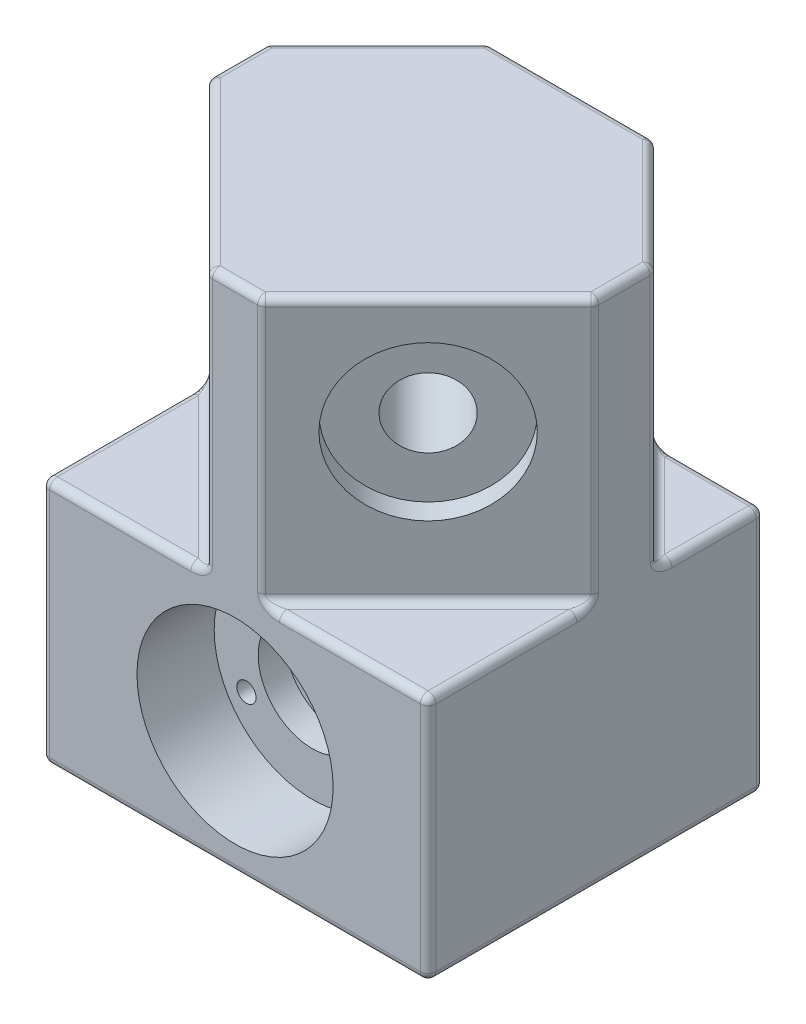
SolidWorks part; units mm, degrees
material "Stainless Steel (ferritic)"
ref_plane "Front Plane" through (0, 0, 0) normal (0, 0, 1) x (1, 0, 0)
ref_plane "Top Plane" through (0, 0, 0) normal (0, 1, 0) x (1, 0, 0)
ref_plane "Right Plane" through (0, 0, 0) normal (1, 0, 0) x (0, 0, -1)
sketch "Sketch1" plane through (0, 0, 0) normal (0, 1, 0) x (1, 0, 0)
  line L0 (-31.75, 31.75) -> (31.75, -31.75) construction
  line L1 (-31.75, 31.75) -> (31.75, 31.75)
  line L2 (-31.75, 31.75) -> (-31.75, -31.75)
  line L3 (-31.75, -31.75) -> (31.75, -31.75)
  line L4 (31.75, 31.75) -> (31.75, -31.75)
  dimension "D1" = 63.5
extrude "Boss-Extrude1" add sketch "Sketch1" along normal blind 66.2
sketch "Sketch2" plane through (0, 0, 31.75) normal (0, 0, 1) x (1, 0, 0)
  line L0 (-31.75, 0) -> (31.75, 0) construction
  circle A0 centre (0, 16) radius 12.7
  dimension "D1" = 25.4
  dimension "D2" = 16
extrude "Cut-Extrude4" cut sketch "Sketch2" against normal blind 10
sketch "Sketch3" plane through (0, 0, 21.75) normal (0, 0, 1) x (1, 0, 0)
  circle A0 centre (0, 16) radius 7
  dimension "D1" = 14
extrude "Cut-Extrude5" cut sketch "Sketch3" against normal blind 3.5
sketch "Sketch4" plane through (0, 0, 18.25) normal (0, 0, 1) x (1, 0, 0)
  circle A0 centre (0, 16) radius 6
  circle A1 centre (0, 16) radius 7 construction
  dimension "D1" = 1
extrude "Cut-Extrude6" cut sketch "Sketch4" against normal through all
sketch "Sketch5" plane through (0, 66.2, 0) normal (0, 1, 0) x (1, 0, 0)
  line L0 (0, -34.6734) -> (0, 38.8135) construction
  line L1 (13.935, -21.1434) -> (3.3284, -10.5368) construction
  line L2 (-31.75, -31.75) -> (31.75, -31.75) construction
  line L3 (3.3284, -31.75) -> (31.75, -3.3284)
  line L4 (31.75, -31.75) -> (31.75, 31.75) construction
  line L5 (31.75, -3.3284) -> (31.75, -31.75)
  line L6 (31.75, -31.75) -> (3.3284, -31.75)
  line L7 (3.3284, -10.5368) -> (0.5, -13.3652) construction
  line L8 (0.5, -13.3652) -> (11.1066, -23.9718) construction
  line L9 (-31.75, -31.75) -> (-3.3284, -31.75)
  line L10 (-31.75, -3.3284) -> (-31.75, -31.75)
  line L11 (-3.3284, -31.75) -> (-31.75, -3.3284)
  dimension "D1" = 45
  dimension "D2" = 15
  dimension "D3" = 4
  dimension "D4" = 15
  dimension "D5" = 0.5
extrude "Cut-Extrude7" cut sketch "Sketch5" against normal offset from surface (34.2 mm away) 32 up to face at (0, 0, 0)
sketch "Sketch6" plane through (0, 0, 31.75) normal (0, 0, 1) x (1, 0, 0)
  line L0 (-31.75, 0) -> (31.75, 0) construction
  line L1 (-31.75, 66.2) -> (-25, 66.2)
  line L2 (-31.75, 66.2) -> (-31.75, 0)
  line L3 (-31.75, 0) -> (-25, 0)
  line L4 (-25, 66.2) -> (-25, 0)
  line L5 (0, 0) -> (0, 78.197) construction
  line L6 (31.75, 0) -> (25, 0)
  line L7 (31.75, 66.2) -> (31.75, 0)
  line L8 (31.75, 66.2) -> (25, 66.2)
  line L9 (25, 66.2) -> (25, 0)
  dimension "D1" = 25
extrude "Cut-Extrude9" cut sketch "Sketch6" against normal through all
sketch "Sketch7" plane through (0, 0, -31.75) normal (0, 0, -1) x (-1, 0, 0)
  line L0 (25, 0) -> (25, 66.2) construction
  line L1 (-25, 66.2) -> (25, 66.2)
  line L2 (-25, 66.2) -> (-25, 0)
  line L3 (-25, 0) -> (25, 0)
  line L4 (25, 66.2) -> (25, 0)
extrude "Cut-Extrude10" cut sketch "Sketch7" against normal blind 20
sketch "Sketch8" plane through (0, 0, -11.75) normal (0, 0, -1) x (-1, 0, 0)
  circle A0 centre (0, 16) radius 12.7
  dimension "D1" = 25.4
extrude "Cut-Extrude11" cut sketch "Sketch8" against normal blind 5
sketch "Sketch9" plane through (0, 66.2, 0) normal (0, 1, 0) x (1, 0, 0)
  line L0 (-25, -2.5784) -> (-10.6716, 11.75)
  line L2 (-25, 11.75) -> (25, 11.75) construction
  line L4 (-25, -2.5784) -> (-25, 11.75)
  line L5 (-25, 11.75) -> (-10.6716, 11.75)
  line L6 (-25, 11.75) -> (-25, -10.0784) construction
  line L7 (-3.3284, -31.75) -> (-25, -10.0784) construction
  dimension "D1" = 7.5
extrude "Cut-Extrude12" cut sketch "Sketch9" against normal up to surface (34.2 mm away) up to face at (-17.7761, 32, 24.5261)
sketch "Sketch10" plane through (-17.5392, 0, 17.5392) normal (-0.7071, 0, 0.7071) x (0.7071, 0, 0.7071)
  line L0 (4.773, 51.2) -> (4.773, 66.2) construction
  line L1 (20.0971, 66.2) -> (-10.5511, 66.2) construction
  circle A0 centre (4.773, 51.2) radius 10
  dimension "D2" = 20
  dimension "D1" = 15
extrude "Cut-Extrude13" cut sketch "Sketch10" against normal blind 3
hole_wizard "M10x1.0 Tapped Hole1" positions "Sketch12" profile "Sketch11" tap size "M10x1.0" standard "Ansi Metric"
sketch "Sketch12" plane through (-15.4179, 0, 15.4179) normal (-0.7071, 0, 0.7071) x (0.7071, 0, 0.7071)
  circle A0 centre (4.773, 51.2) radius 10 construction
  point P0 (4.773, 51.2)
sketch "Sketch11" plane through (-12.0429, 51.2, 18.7929) normal (0, 1, 0) x (0.7071, 0, 0.7071)
  line L0 (0, 0) -> (0, 15.7039)
  line L1 (0, 15.7039) -> (4.5, 13)
  line L2 (4.5, 13) -> (4.5, 0)
  line L5 (4.5, 0) -> (0, 0)
  line L10 (0, 15.7039) -> (-4.5, 13) construction
  line L11 (0, -6.35) -> (0, 107.95) construction
  dimension "Tap Drill Dia." = 9
  dimension "Tap Drill Depth" = 13
  dimension "Drill Angle" = 118
cosmetic thread "Hole Thread1" parameters "D1"=10, "D2"=10
mirror "Mirror1" about plane through (0, 0, 0) normal (1, 0, 0) of "Cut-Extrude12", "M10x1.0 Tapped Hole1", "Cut-Extrude13"
fillet "Fillet3" [suppressed] radius 10
fillet "Fillet4" [suppressed] radius 10
sketch "Sketch13" plane through (0, 0, -6.75) normal (0, 0, -1) x (-1, 0, 0)
  circle A0 centre (0, 16) radius 7
  circle A1 centre (0, 16) radius 7 construction
extrude "Cut-Extrude14" cut sketch "Sketch13" against normal blind 3.5
hole_wizard "M3x0.5 Tapped Hole1" positions "Sketch15" profile "Sketch14" tap size "M3x0.5" standard "Ansi Metric"
sketch "Sketch15" plane through (0, 0, -11.75) normal (0, 0, -1) x (-1, 0, 0)
  line L0 (-19.3722, 3.6018) -> (19.3722, 28.3982) construction
  line L3 (0, 0) -> (0, 16) construction
  line L6 (-25, 0) -> (25, 32) construction
  line L7 (10.6716, 32) -> (25, 32) construction
  line L8 (25, 32) -> (10.6716, 32) construction
  line L10 (25, 0) -> (25, 32) construction
  point P0 (-19.3722, 3.6018)
  point P1 (19.3722, 28.3982)
  dimension "D1" = 46
sketch "Sketch14" plane through (19.3722, 3.6018, -11.75) normal (1, 0, 0) x (0, 1, 0)
  line L0 (0, 0) -> (0, 22.7511)
  line L1 (0, 22.7511) -> (1.25, 22)
  line L2 (1.25, 22) -> (1.25, 0)
  line L5 (1.25, 0) -> (0, 0)
  line L10 (0, 22.7511) -> (-1.25, 22) construction
  line L11 (0, -6.35) -> (0, 107.95) construction
  dimension "Tap Drill Dia." = 2.5
  dimension "Tap Drill Depth" = 22
  dimension "Drill Angle" = 118
cosmetic thread "Hole Thread2" parameters "D1"=12, "D2"=3
cosmetic thread "Hole Thread3" parameters "D1"=12, "D2"=3
fillet "Fillet5" radius 1 36 edges at (3.3284, 49.1, 31.75) (-3.3284, 49.1, 31.75) (-17.8358, 32, -11.75) (17.8358, 32, -11.75) (0, 0, 31.75) (0, 0, -11.75) (14.1642, 66.2, 20.9142) (0, 66.2, 31.75) (-14.1642, 66.2, 20.9142) (0, 66.2, -11.75) (14.1642, 32, 31.75) (14.1642, 32, 20.9142) (-14.1642, 32, 20.9142) (-14.1642, 32, 31.75) (-25, 49.1, 10.0784) (-25, 32, 20.9142) (-25, 16, 31.75) (-25, 0, 10) (-25, 16, -11.75) (-25, 32, -4.5858) (-25, 66.2, 6.3284) (-10.6716, 49.1, -11.75) (-17.8358, 66.2, -4.5858) (-25, 49.1, 2.5784) (-17.8358, 32, -4.5858) (17.8358, 32, -4.5858) (17.8358, 66.2, -4.5858) (10.6716, 49.1, -11.75) (25, 32, -4.5858) (25, 16, -11.75) (25, 0, 10) (25, 16, 31.75) (25, 32, 20.9142) (25, 49.1, 10.0784) (25, 66.2, 6.3284) (25, 49.1, 2.5784)
hole_wizard "M3x0.5 Tapped Hole2" positions "Sketch17" profile "Sketch16" tap size "M3x0.5" standard "Ansi Metric"
sketch "Sketch17" plane through (0, 0, 21.75) normal (0, 0, 1) x (1, 0, 0)
  line L0 (-8.5304, 11.075) -> (0, 16) construction
  line L1 (0, 16) -> (0, 25.85) construction
  line L4 (0, 16) -> (8.5304, 11.075) construction
  line L6 (0, 23) -> (0, 28.7) construction
  circle A1 centre (0, 16) radius 7 construction
  circle A2 centre (0, 16) radius 7 construction
  circle A3 centre (0, 16) radius 12.7 construction
  point P0 (0, 25.85)
  point P1 (-8.5304, 11.075)
  point P3 (8.5304, 11.075)
  dimension "D1" = 120
  dimension "D2" = 120
sketch "Sketch16" plane through (0, 25.85, 21.75) normal (1, 0, 0) x (0, -1, 0)
  line L0 (0, 0) -> (0, 22.7511)
  line L1 (0, 22.7511) -> (1.25, 22)
  line L2 (1.25, 22) -> (1.25, 0)
  line L5 (1.25, 0) -> (0, 0)
  line L10 (0, 22.7511) -> (-1.25, 22) construction
  line L11 (0, -6.35) -> (0, 107.95) construction
  dimension "Tap Drill Dia." = 2.5
  dimension "Tap Drill Depth" = 22
  dimension "Drill Angle" = 118
cosmetic thread "Hole Thread4" parameters "D1"=12, "D2"=3
cosmetic thread "Hole Thread5" parameters "D1"=12, "D2"=3
cosmetic thread "Hole Thread6" parameters "D1"=12, "D2"=3
cosmetic thread "Hole Thread8" parameters "D1"=12, "D2"=3
hole_wizard "M3x0.5 Tapped Hole3" positions "Sketch19" profile "Sketch18" tap size "M3x0.5" standard "Ansi Metric"
sketch "Sketch19" plane through (0, 0, -6.75) normal (0, 0, -1) x (-1, 0, 0)
  line L0 (0, 23) -> (0, 28.7) construction
  line L2 (0, 16) -> (-8.5304, 11.075) construction
  line L5 (0, 16) -> (8.5304, 11.075) construction
  line L7 (0, 25.85) -> (0, 16) construction
  circle A0 centre (0, 16) radius 7 construction
  circle A1 centre (0, 16) radius 7 construction
  circle A2 centre (0, 16) radius 12.7 construction
  point P0 (0, 25.85)
  point P1 (-8.5304, 11.075)
  point P3 (8.5304, 11.075)
  dimension "D1" = 120
  dimension "D2" = 120
sketch "Sketch18" plane through (0, 25.85, -6.75) normal (1, 0, 0) x (0, 1, 0)
  line L0 (0, 0) -> (0, 22.7511)
  line L1 (0, 22.7511) -> (1.25, 22)
  line L2 (1.25, 22) -> (1.25, 0)
  line L5 (1.25, 0) -> (0, 0)
  line L10 (0, 22.7511) -> (-1.25, 22) construction
  line L11 (0, -6.35) -> (0, 107.95) construction
  dimension "Tap Drill Dia." = 2.5
  dimension "Tap Drill Depth" = 22
  dimension "Drill Angle" = 118
cosmetic thread "Hole Thread7" parameters "D1"=12, "D2"=3
cosmetic thread "Hole Thread9" parameters "D1"=12, "D2"=3
